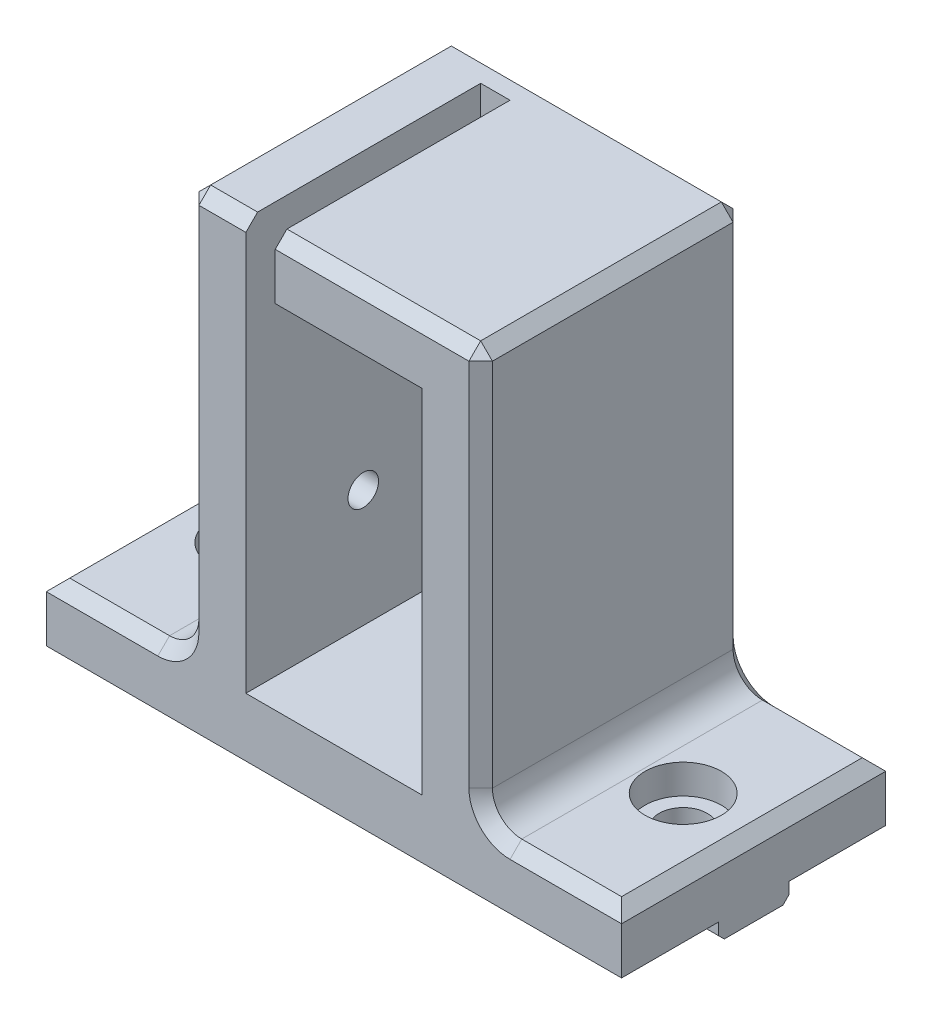
SolidWorks part; units mm, degrees
ref_plane "Płaszczyzna przednia" through (0, 0, 0) normal (0, 0, 1) x (1, 0, 0)
ref_plane "Płaszczyzna górna" through (0, 0, 0) normal (0, 1, 0) x (1, 0, 0)
ref_plane "Płaszczyzna prawa" through (0, 0, 0) normal (1, 0, 0) x (0, 0, -1)
sketch "Sketch1" plane through (0, 0, 0) normal (0, 0, 1) x (1, 0, 0)
  line L1 (0, 0) -> (0, 80)
  line L3 (50, 80) -> (50, 0)
  line L14 (0, 0) -> (50, 0)
  line L15 (0, 80) -> (10, 80)
  line L18 (10, 80) -> (10, 10)
  line L19 (10, 10) -> (40, 10)
  line L22 (40, 10) -> (40, 70)
  line L23 (40, 70) -> (15, 70)
  line L24 (15, 70) -> (15, 80)
  line L25 (15, 80) -> (50, 80)
  point P0 (49.517, 60)
  dimension "D1" = 10
  dimension "D2" = 10
  dimension "D3" = 10
  dimension "D4" = 10
  dimension "D5" = 50
  dimension "D6" = 5
  dimension "D7" = 80
extrude "Boss-Extrude1" add sketch "Sketch1" along normal blind 40
sketch "Sketch2" plane through (0, 0, 0) normal (1, 0, 0) x (0, 0, -1)
  line L0 (-40, 0) -> (-40, 80) construction
  circle A0 centre (-20, 30) radius 2.6
  dimension "D3" = 5.2
  dimension "D1" = 20
  dimension "D2" = 30
extrude "Cut-Extrude1" cut sketch "Sketch2" against normal through all from surface starting at face at (10, 45, 20)
sketch "Sketch9" plane through (0, 0, 0) normal (0, 0, 1) x (1, 0, 0)
  line L0 (50, 80) -> (15, 80) construction
  line L2 (50, 80) -> (50, 0)
  line L3 (50, 0) -> (0, 0)
  line L4 (0, 80) -> (0, 0)
  line L5 (50, 0) -> (50, 80) construction
  line L6 (50, 80) -> (0, 80)
extrude "Boss-Extrude2" add sketch "Sketch9" against normal blind 5
sketch "Sketch11" plane through (0, 0, 0) normal (0, 1, 0) x (1, 0, 0)
  line L0 (50, -40) -> (50, 5) construction
  line L9 (0, 5) -> (50, 5) construction
  line L10 (0, -40) -> (0, 5) construction
  line L11 (10, -40) -> (0, -40) construction
  line L12 (50, 5) -> (74, 5)
  line L13 (50, 5) -> (50, -40)
  line L14 (50, -40) -> (74, -40)
  line L15 (74, 5) -> (74, -40)
  line L16 (0, 5) -> (-24, 5)
  line L17 (0, 5) -> (0, -40)
  line L18 (0, -40) -> (-24, -40)
  line L19 (-24, 5) -> (-24, -40)
  point P4 (0, 0)
  dimension "D1" = 24
  dimension "D2" = 24
extrude "Boss-Extrude3" add sketch "Sketch11" along normal blind 10 from surface starting at face at (25, 0, 17.5)
sketch "Sketch12" plane through (0, 0, 0) normal (0, 1, 0) x (1, 0, 0)
  line L3 (-24, -40) -> (0, -40) construction
  line L4 (-24, 5) -> (-24, -40) construction
  line L6 (74, -40) -> (74, 5) construction
  circle A0 centre (-12, -17.5) radius 4.1
  circle A1 centre (62, -17.5) radius 4.1
  dimension "D2" = 8.2
  dimension "D1" = 22.5
  dimension "D3" = 12
  dimension "D4" = 12
extrude "Cut-Extrude2" cut sketch "Sketch12" along normal through all both and the other way through all
sketch "Sketch13" plane through (0, 0, 0) normal (0, 1, 0) x (1, 0, 0)
  circle A0 centre (-12, -17.5) radius 6.5
  circle A1 centre (62, -17.5) radius 6.5
  dimension "D1" = 13
  dimension "D2" = 13
extrude "Cut-Extrude3" cut sketch "Sketch13" against normal blind 5 from surface starting at face at (-12, 10, 13.4)
fillet "Fillet2" radius 5 2 edges at (50, 10, 17.5) (0, 10, 17.5)
chamfer "Chamfer1" distance 2 angle 45 19 edges at (-24, 10, 17.5) (-14.5, 10, -5) (-1.4645, 11.4645, -5) (0, 47.5, -5) (50, 47.5, -5) (51.4645, 11.4645, -5) (64.5, 10, -5) (74, 10, 17.5) (64.5, 10, 40) (51.4645, 11.4645, 40) (50, 47.5, 40) (32.5, 80, 40) (-14.5, 10, 40) (-1.4645, 11.4645, 40) (5, 80, 40) (0, 47.5, 40) (50, 80, 17.5) (25, 80, -5) (0, 80, 17.5)
sketch "Sketch14" plane through (0, 0, 0) normal (0, 1, 0) x (1, 0, 0)
  line L0 (-24, -40) -> (-24, 5) construction
  line L1 (-24, -23.5) -> (74, -23.5)
  line L2 (-24, -23.5) -> (-24, -11.5)
  line L3 (-24, -11.5) -> (74, -11.5)
  line L4 (74, -23.5) -> (74, -11.5)
  line L5 (74, 5) -> (74, -40) construction
  dimension "D1" = 12
  dimension "D2" = 16.5
extrude "Boss-Extrude4" add sketch "Sketch14" against normal blind 3
extrude "Cut-Extrude4" cut sketch "Sketch12<2>" along normal through all both and the other way through all
sketch "Sketch12<2>" plane through (0, 0, 0) normal (0, 1, 0) x (1, 0, 0) same geometry as "Sketch12"
chamfer "Chamfer2" distance 1 angle 45 2 edges at (25, -3, 11.5) (25, -3, 23.5)
